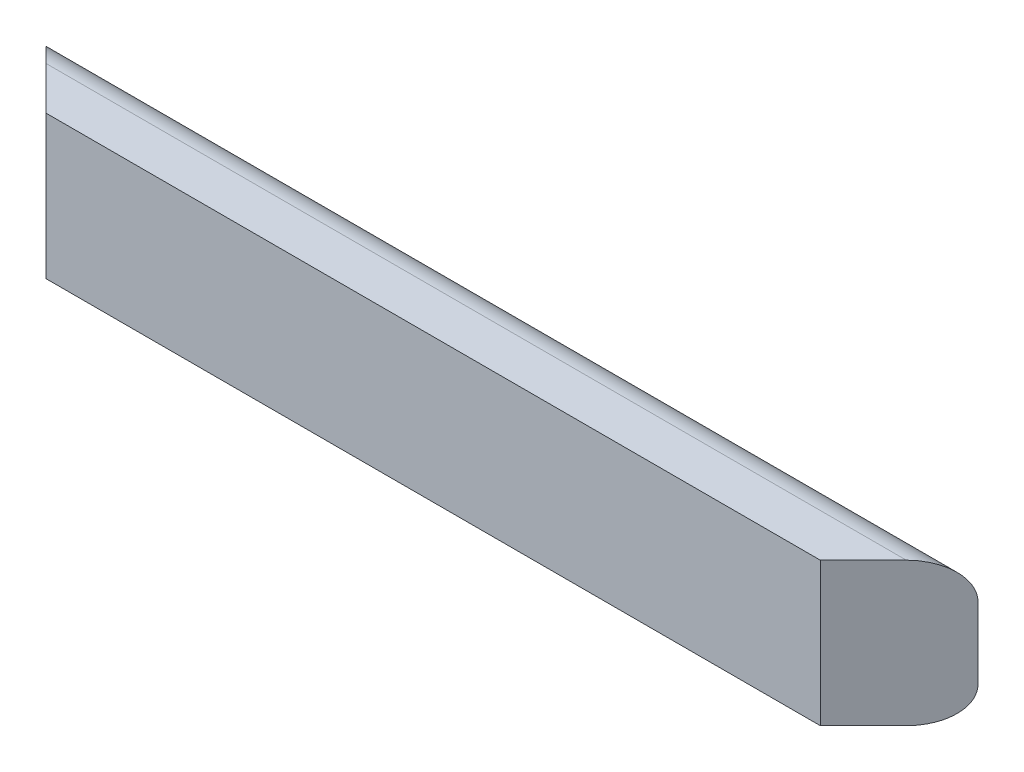
SolidWorks part; units mm, degrees
material "Custom Plastic"
ref_plane "Front Plane" through (0, 0, 0) normal (0, 0, 1) x (1, 0, 0)
ref_plane "Top Plane" through (0, 0, 0) normal (0, 1, 0) x (1, 0, 0)
ref_plane "Right Plane" through (0, 0, 0) normal (1, 0, 0) x (0, 0, -1)
sketch "Sketch1" plane through (0, 0, 0) normal (1, 0, 0) x (0, 0, -1)
  line L0 (6.35, 127) -> (38.1, 127)
  line L1 (0, 0) -> (6.35, 0)
  line L2 (0, 0) -> (0, 127)
  line L3 (0, 127) -> (6.35, 127)
  line L5 (69.85, 95.25) -> (69.85, 31.75)
  line L6 (38.1, 0) -> (6.35, 0)
  arc A0 (69.85, 95.25) -> (38.1, 127) centre (38.1, 95.25) ccw
  arc A1 (38.1, 0) -> (69.85, 31.75) centre (38.1, 31.75) ccw
  dimension "D3" = 63.5
  dimension "D5" = 31.75
  dimension "D1" = 127
  dimension "D2" = 6.35
  dimension "D4" = 31.75
extrude "Boss-Extrude1" add sketch "Sketch1" along normal blind 412.75 and the other way blind 412.75
sketch "Sketch2" plane through (0, 127, 0) normal (0, 1, 0) x (1, 0, 0)
  line L0 (412.75, 69.85) -> (342.9, 0)
  line L1 (-55, 0) -> (55, 0) construction
  line L2 (-412.75, 69.85) -> (-342.9, 0)
  line L3 (-412.75, 69.85) -> (-412.75, 0)
  line L4 (-412.75, 38.1) -> (-412.75, 0) construction
  line L5 (-412.75, 0) -> (-342.9, 0)
  line L6 (412.75, 69.85) -> (412.75, 0)
  line L7 (412.75, 38.1) -> (412.75, 0) construction
  line L8 (412.75, 0) -> (342.9, 0)
  dimension "D1" = 45
  dimension "D2" = 45
extrude "Cut-Extrude1" cut sketch "Sketch2" against normal through all
sketch "Sketch3" plane through (0, 0, -69.85) normal (0, 0, -1) x (-1, 0, 0)
  line L0 (0, 38.4175) -> (0, -38.4175) construction
  line L1 (38.4175, 0) -> (-38.4175, 0) construction
  text T0 "3597" font "Arial" height in points 250
  dimension "D1" = 144.78
  dimension "D2" = 31.75
extrude "Boss-Extrude2" add sketch "Sketch3" along normal blind 0.254
